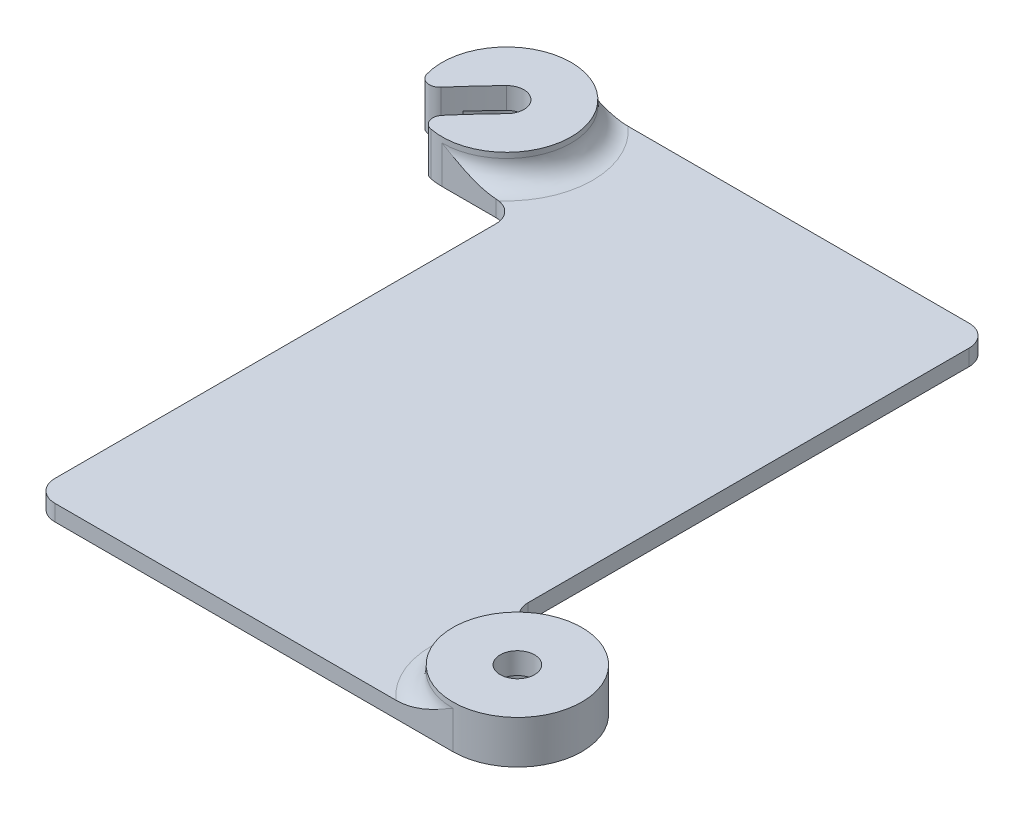
SolidWorks part; units mm, degrees
material "ABS"
ref_plane "Plan de face" through (0, 0, 0) normal (0, 0, 1) x (1, 0, 0)
ref_plane "Plan de dessus" through (0, 0, 0) normal (0, 1, 0) x (1, 0, 0)
ref_plane "Plan de droite" through (0, 0, 0) normal (1, 0, 0) x (0, 0, -1)
sketch "Esquisse1" plane through (0, 0, 0) normal (0, 1, 0) x (1, 0, 0)
  line L1 (-16, 57) -> (16, 57)
  line L2 (-16, 57) -> (-16, 0)
  line L3 (-16, 0) -> (16, 0)
  line L4 (16, 57) -> (16, 0)
  dimension "D1" = 57
  dimension "D2" = 32
extrude "Boss.-Extru.1" add sketch "Esquisse1" along normal blind 1.5
sketch "Esquisse2" plane through (0, 0, 0) normal (0, 1, 0) x (1, 0, 0)
  line L0 (-16, 57) -> (-16, 45)
  line L1 (16, 12) -> (23, 12)
  line L2 (16, 0) -> (23, 0)
  line L3 (16, 0) -> (16, 57) construction
  line L4 (16, 0) -> (16, 12)
  line L5 (-16, 57) -> (-16, 0) construction
  line L6 (-16, 45) -> (-23, 45)
  line L7 (-23, 57) -> (-16, 57)
  arc A0 (-23, 45) -> (-23, 57) centre (-23, 51) cw
  arc A1 (23, 0) -> (23, 12) centre (23, 6) ccw
  dimension "D2" = 6
  dimension "D1" = 23
extrude "Boss.-Extru.2" add sketch "Esquisse2" along normal up to surface (1.5 mm away) up to face at (0, 1.5, -28.5)
sketch "Esquisse3" plane through (0, 0, 0) normal (0, 1, 0) x (1, 0, 0)
  circle A0 centre (-23, 51) radius 6
  circle A1 centre (23, 6) radius 6
  arc A2 (23, 0) -> (23, 12) centre (23, 6) ccw construction
  arc A4 (-23, 57) -> (-23, 45) centre (-23, 51) ccw construction
extrude "Boss.-Extru.3" add sketch "Esquisse3" along normal blind 4
fillet "Congé2" radius 2 4 edges at (16, 0.75, -57) (-16, 0.75, 0)
fillet "Congé1" radius 2 2 edges at (17, 1.5, -6) (-17, 1.5, -51)
hole_wizard "Chambrage pour vis à tête cylindrique à 6 pans creux (ou vis CHC) M31" positions "Esquisse5" profile "Esquisse4" counterbore size "M3" standard "Ansi Metric" end condition through all
sketch "Esquisse5" plane through (0, 0, 0) normal (0, -1, 0) x (-1, 0, 0)
  arc A0 (-23, 12) -> (-23, 0) centre (-23, 6) ccw construction
  circle A2 centre (23, 51) radius 6 construction
  point P0 (23, 51)
  point P2 (-23, 6)
sketch "Esquisse4" plane through (-23, 0, -51) normal (1, 0, 0) x (0, 0, -1)
  line L0 (0, 0) -> (0, 4.088)
  line L1 (0, 4.088) -> (1.6, 4.088)
  line L3 (1.6, 4.088) -> (1.6, 2)
  line L4 (1.6, 2) -> (3.25, 2)
  line L5 (3.25, 2) -> (3.25, 0)
  line L7 (3.25, 0) -> (0, 0)
  line L11 (0, -6.35) -> (0, 107.95) construction
  dimension "Diamètre du perçage jusqu'au prochain" = 3.2
  dimension "Profondeur du perçage jusqu'au prochain" = 4.088
  dimension "Diamètre du chambrage" = 6.5
  dimension "Profondeur du chambrage" = 2
sketch "Esquisse6" plane through (0, 4, 0) normal (0, 1, 0) x (1, 0, 0)
  line L0 (-14, 0) -> (17.7085, 0) construction
  arc A0 (-41.0703, 0) -> (-23, 51) centre (23, 6) cw construction
  arc A1 (-24.1437, 52.1189) -> (-42.6633, -0.1492) centre (23, 6) ccw
  arc A2 (-21.8563, 49.8811) -> (-39.4772, 0.1492) centre (23, 6) ccw
  arc A3 (-21.8563, 49.8811) -> (-24.1437, 52.1189) centre (-23, 51) ccw
  arc A4 (-42.6633, -0.1492) -> (-39.4772, 0.1492) centre (-41.0703, 0) ccw
  circle A5 centre (23, 6) radius 1.6 construction
  circle A6 centre (-23, 51) radius 1.6 construction
  point P3 (-37.6557, 27.4915)
extrude "Enlèv. mat.-Extru.2" cut sketch "Esquisse6" against normal through all
fillet "Congé3" radius 1 2 edges at (-28.0478, 2, -47.7565) (-25.6596, 2, -45.6217)
